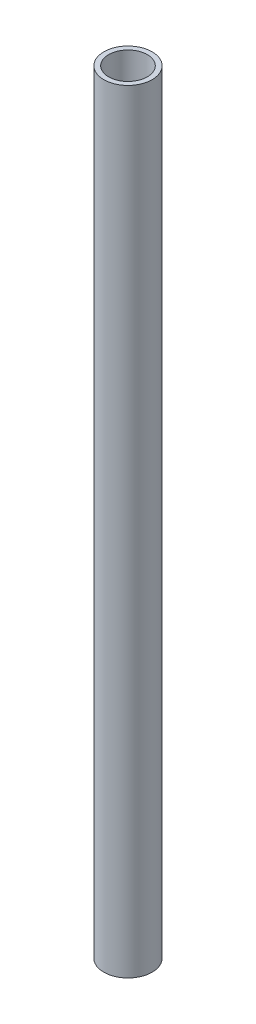
SolidWorks part; units mm, degrees
material "Carbon Tube"
ref_plane "Front Plane" through (0, 0, 0) normal (0, 0, 1) x (1, 0, 0)
ref_plane "Top Plane" through (0, 0, 0) normal (0, 1, 0) x (1, 0, 0)
ref_plane "Right Plane" through (0, 0, 0) normal (1, 0, 0) x (0, 0, -1)
sketch "Sketch1" plane through (0, 0, 0) normal (0, 1, 0) x (1, 0, 0)
  circle A0 centre (0, 0) radius 3.175
  circle A1 centre (0, 0) radius 2.54
  dimension "D1" = 6.35
  dimension "D2" = 5.08
extrude "Boss-Extrude1" add sketch "Sketch1" along normal blind 101.6
ref_axis "Axis1" through (0, 101.6, 0) along (0, -1, 0)
